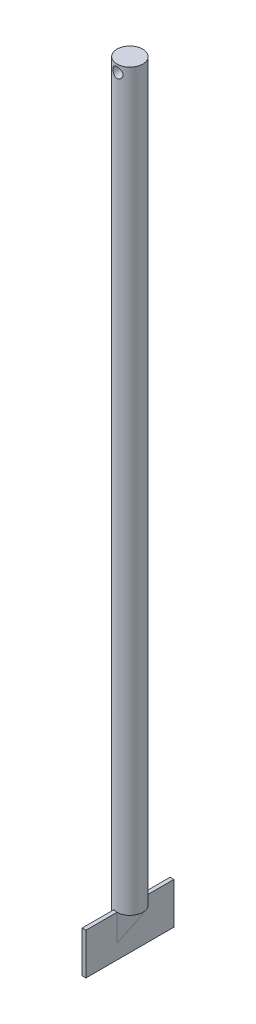
SolidWorks part; units mm, degrees
ref_plane "Front Plane" through (0, 0, 0) normal (0, 0, 1) x (1, 0, 0)
ref_plane "Top Plane" through (0, 0, 0) normal (0, 1, 0) x (1, 0, 0)
ref_plane "Right Plane" through (0, 0, 0) normal (1, 0, 0) x (0, 0, -1)
sketch "Sketch1" plane through (0, 0, 0) normal (0, 1, 0) x (1, 0, 0)
  circle A0 centre (0, 0) radius 2.5
  dimension "D1" = 5
extrude "Boss-Extrude1" add sketch "Sketch1" along normal blind 150
sketch "Sketch2" plane through (0, 0, 0) normal (0, -1, 0) x (1, 0, 0)
  line L0 (0, -2.5) -> (0, 2.5)
  arc A0 (0, -2.5) -> (0, 2.5) centre (0, 0) ccw
extrude "Cut-Extrude1" cut sketch "Sketch2" against normal blind 8 normal cut yes
sketch "Sketch4" plane through (0, 0, 0) normal (1, 0, 0) x (0, 0, -1)
  line L1 (-2.5, 8) -> (-8.5, 8)
  line L2 (-2.5, 0) -> (-8.5, 0)
  line L3 (-8.5, 8) -> (-8.5, 0)
  line L5 (2.5, 8) -> (8.5, 8)
  line L6 (2.5, 0) -> (8.5, 0)
  line L7 (8.5, 8) -> (8.5, 0)
  line L8 (2.5, 0) -> (-2.5, 0)
  line L9 (2.5, 8) -> (-2.5, 8)
  dimension "D1" = 6
  dimension "D2" = 6
base flange "Base-Flange1" sketch "Sketch4" thickness 0.7366 reverse thickness direction no parameters "D1"=0.7366
sketch "Sketch9" plane through (0, 0, 0) normal (0, 0, 1) x (1, 0, 0)
  circle A0 centre (0, 148.5698) radius 0.9765
extrude "Cut-Extrude2" cut sketch "Sketch9" against normal through all both and the other way through all normal cut yes
sketch "Bend-Lines1" plane through (0, 0, 0) normal (0, 1, 0) x (1, 0, 0)
sketch "Bounding-Box1" plane through (0, 0, 0) normal (0, 1, 0) x (1, 0, 0)
sheet metal parameters "Sheet-Metal3" thickness 0.7366 parameters "D1"=0.7366
flat pattern "Flat-Pattern3" [suppressed]
sketch "Bend-Lines2" plane through (0, 0, 0) normal (0, 1, 0) x (1, 0, 0)
sketch "Bounding-Box2" [suppressed] plane through (0, 0, 0) normal (0, 1, 0) x (1, 0, 0)
